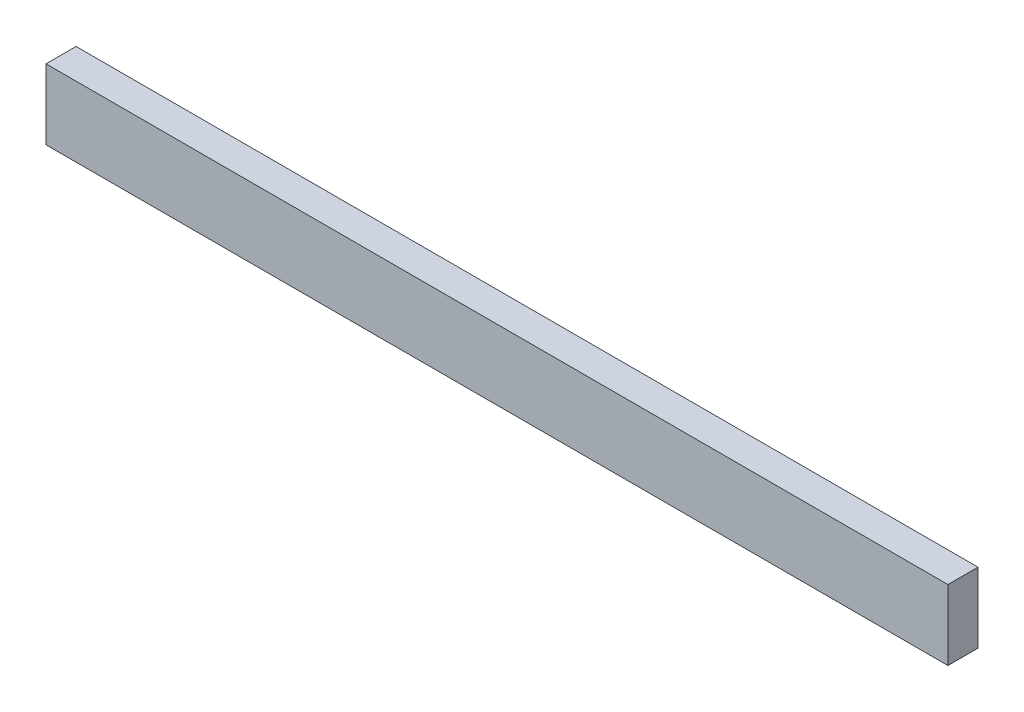
SolidWorks part; units mm, degrees
ref_plane "Front Plane" through (0, 0, 0) normal (0, 0, 1) x (1, 0, 0)
ref_plane "Top Plane" through (0, 0, 0) normal (0, 1, 0) x (1, 0, 0)
ref_plane "Right Plane" through (0, 0, 0) normal (1, 0, 0) x (0, 0, -1)
sketch "Sketch1" plane through (0, 0, 0) normal (0, 0, 1) x (1, 0, 0)
  line L1 (-571.5, 44.45) -> (571.5, 44.45)
  line L2 (-571.5, 44.45) -> (-571.5, -44.45)
  line L3 (-571.5, -44.45) -> (571.5, -44.45)
  line L4 (571.5, 44.45) -> (571.5, -44.45)
  line L5 (-571.5, 44.45) -> (571.5, -44.45) construction
  line L6 (-571.5, -44.45) -> (571.5, 44.45) construction
  point P0 (0, 0)
  dimension "D1" = 1143
  dimension "D2" = 88.9
extrude "Boss-Extrude1" add sketch "Sketch1" along normal blind 19.05 and the other way blind 19.05
